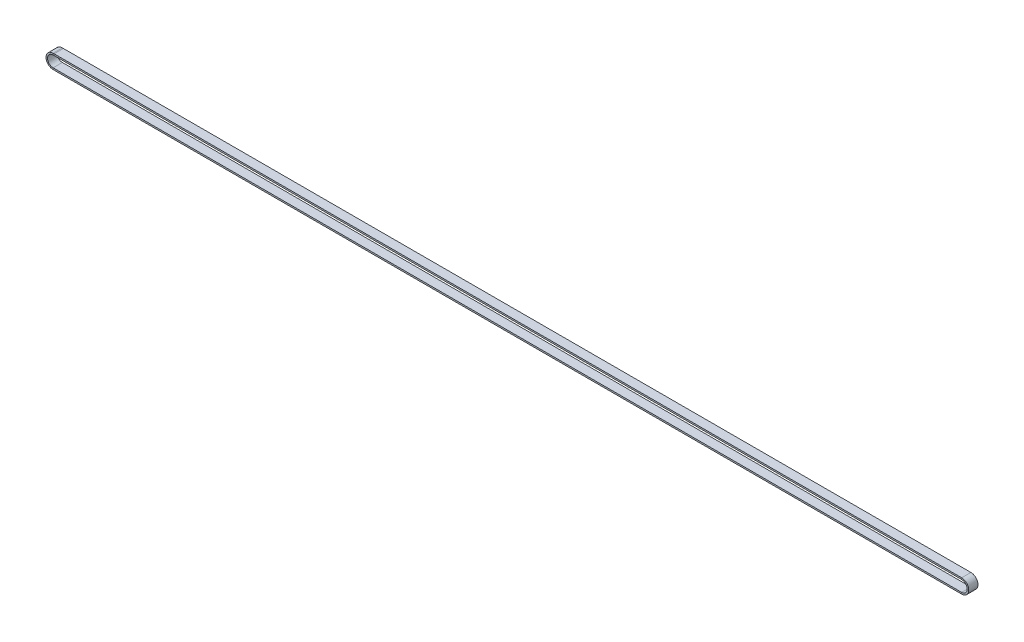
SolidWorks part; units mm, degrees
ref_plane "Front Plane" through (0, 0, 0) normal (0, 0, 1) x (1, 0, 0)
ref_plane "Top Plane" through (0, 0, 0) normal (0, 1, 0) x (1, 0, 0)
ref_plane "Right Plane" through (0, 0, 0) normal (1, 0, 0) x (0, 0, -1)
sketch "Sketch2" plane through (0, 0, -43.9834) normal (0, 0, 1) x (1, 0, 0)
  line L0 (0, 0) -> (1, 0) construction
  line L1 (0, 0) -> (0, 1) construction
  line L2 (-1, -57.9797) -> (883.5206, -57.9797)
  line L3 (883.5206, -71.7797) -> (-1, -71.7797)
  arc A0 (-1, -71.7797) -> (-1, -57.9797) centre (-1, -64.8797) cw
  arc A1 (883.5206, -57.9797) -> (883.5206, -71.7797) centre (883.5206, -64.8797) cw
sketch "Sketch3" plane through (0, 0, 0) normal (1, 0, 0) x (0, 0, -1)
  line L1 (43.9834, -59.4797) -> (34.9834, -59.4797)
  line L2 (43.9834, -59.4797) -> (43.9834, -57.9797)
  line L3 (43.9834, -57.9797) -> (34.9834, -57.9797)
  line L4 (34.9834, -59.4797) -> (34.9834, -57.9797)
  dimension "D1" = 9
  dimension "D2" = 1.5
sweep "Sweep1" add profiles "Sketch3" path "Sketch2"
